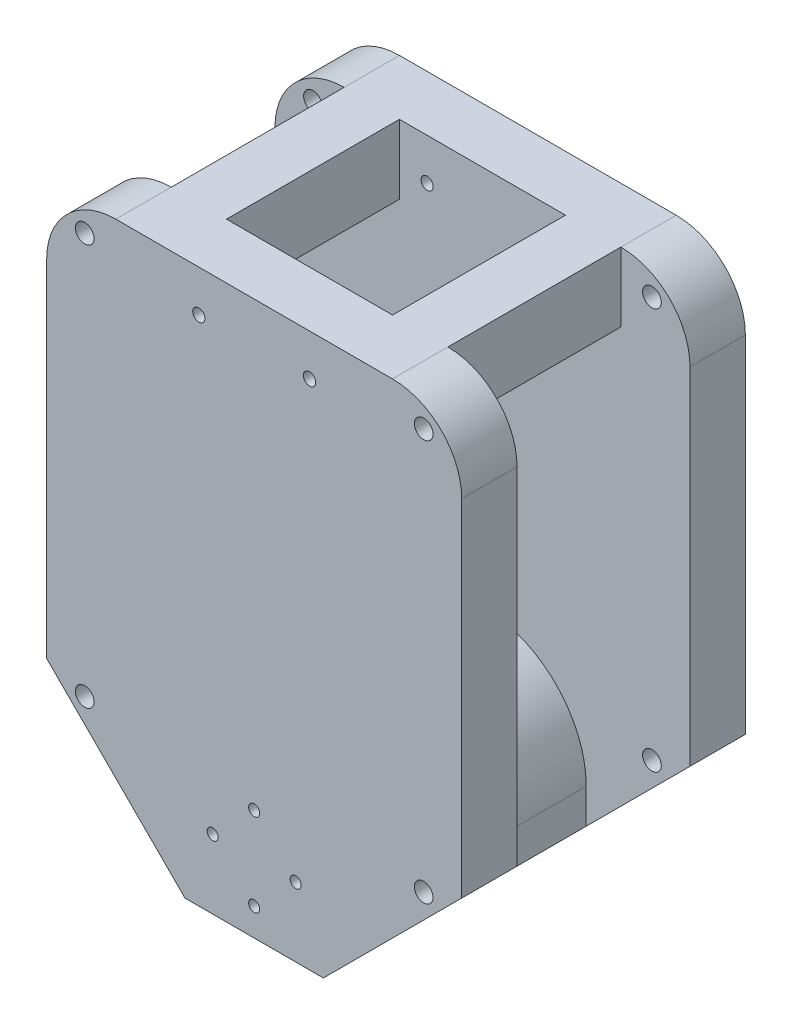
SolidWorks part; units mm, degrees
ref_plane "Front Plane" through (0, 0, 0) normal (0, 0, 1) x (1, 0, 0)
ref_plane "Top Plane" through (0, 0, 0) normal (0, 1, 0) x (1, 0, 0)
ref_plane "Right Plane" through (0, 0, 0) normal (1, 0, 0) x (0, 0, -1)
sketch "Sketch1" plane through (0, 0, 0) normal (0, 0, 1) x (1, 0, 0)
  line L11 (-30, 20.2064) -> (0, 20.2064)
  line L12 (0, 20.2064) -> (30, 20.2064)
  line L13 (30, 20.2064) -> (30, -59.7936)
  line L14 (30, -59.7936) -> (-30, -59.7936)
  line L15 (-30, -59.7936) -> (-30, 20.2064)
  circle A0 centre (-8, 14.2064) radius 0.8836
  circle A1 centre (8, 14.2064) radius 0.8966
  circle A2 centre (0, -49.7936) radius 8 construction
  circle A3 centre (0, -49.7936) radius 6 construction
  circle A4 centre (0, -43.7936) radius 0.8
  circle A5 centre (6, -49.7936) radius 0.8
  circle A6 centre (0, -55.7936) radius 0.8
  circle A7 centre (-6, -49.7936) radius 0.8
  circle A8 centre (-24.5, 16.2064) radius 1.35
  circle A9 centre (24.5, 16.2064) radius 1.35
  circle A10 centre (-24.5, -41.7936) radius 1.35
  circle A11 centre (24.5, -41.7936) radius 1.35
  point P25 (0, -49.7936)
  dimension "D7" = 4
  dimension "D10" = 49
  dimension "D1" = 8
  dimension "D2" = 30
  dimension "D3" = 30
  dimension "D4" = 16
  dimension "D5" = 0
  dimension "D6" = 80
  dimension "D8" = 10
  dimension "D9" = 6
  dimension "D11" = 24.5
  dimension "D12" = 58
  dimension "D13" = 4
extrude "Boss-Extrude1" add sketch "Sketch1" along normal blind 8
sketch "Sketch2" plane through (0, 0, 8) normal (0, 0, 1) x (1, 0, 0)
  line L0 (-12, 20.2064) -> (-12, 10.2064)
  line L1 (30, 20.2064) -> (-30, 20.2064) construction
  line L2 (12, 20.2064) -> (12, 10.2064)
  line L3 (12, 20.2064) -> (20, 20.2064)
  line L4 (20, 20.2064) -> (20, 10.2064)
  line L5 (20, 10.2064) -> (12, 10.2064)
  line L6 (-12, 20.2064) -> (-20, 20.2064)
  line L7 (-20, 20.2064) -> (-20, 10.2064)
  line L8 (-20, 10.2064) -> (-12, 10.2064)
  dimension "D1" = 12
  dimension "D2" = 12
  dimension "D3" = 10
  dimension "D4" = 8
  dimension "D5" = 8
extrude "Boss-Extrude3" add sketch "Sketch2" along normal blind 25
extrude "Boss-Extrude4" add sketch "Sketch1<2>" against normal blind 8 from offset 41
sketch "Sketch1<2>" plane through (0, 0, 0) normal (0, 0, 1) x (1, 0, 0) same geometry as "Sketch1"
sketch "Sketch3" plane through (0, 0, 8) normal (0, 0, 1) x (1, 0, 0)
  line L4 (-30, -59.7936) -> (-10, -59.7936) construction
  line L5 (-6, -49.7936) -> (6, -49.7936) construction
  line L6 (-10, -49.7936) -> (-10, -59.7936)
  line L7 (0, -43.7936) -> (0, -55.7936) construction
  line L8 (10, -49.7936) -> (10, -59.7936)
  line L9 (10, -59.7936) -> (30, -59.7936) construction
  line L10 (-10, -59.7936) -> (10, -59.7936)
  arc A1 (10, -49.7936) -> (-10, -49.7936) centre (0, -49.7936) ccw
extrude "Cut-Extrude1" cut sketch "Sketch3" against normal blind 3
extrude "Cut-Extrude2" cut sketch "Sketch3<2>" along normal blind 3 from surface starting at face at (25.85, -41.7936, 33)
sketch "Sketch3<2>" plane through (0, 0, 8) normal (0, 0, 1) x (1, 0, 0) same geometry as "Sketch3"
sketch "Sketch4" plane through (0, 0, 33) normal (0, 0, -1) x (-1, 0, 0)
  line L0 (-15, -49.7936) -> (-15, -59.7936)
  line L1 (15, -49.7936) -> (15, -59.7936)
  line L2 (-10, -49.7936) -> (-10, -59.7936)
  line L3 (15, -59.7936) -> (30, -59.7936)
  line L4 (-15, -59.7936) -> (-10, -59.7936)
  line L5 (10, -49.7936) -> (10, -59.7936)
  line L6 (-15, -59.7936) -> (-10, -59.7936)
  line L7 (10, -59.7936) -> (15, -59.7936)
  line L8 (15, -59.7936) -> (10, -59.7936)
  line L10 (-15, -59.7936) -> (-10, -59.7936)
  line L11 (10, -59.7936) -> (15, -59.7936)
  line L15 (-30, -59.7936) -> (-10, -59.7936)
  line L16 (-10, -59.7936) -> (-10, -49.7936)
  line L17 (10, -49.7936) -> (10, -59.7936)
  line L18 (10, -59.7936) -> (30, -59.7936)
  line L19 (30, -59.7936) -> (30, 20.2064)
  line L20 (30, 20.2064) -> (20, 20.2064)
  line L21 (20, 20.2064) -> (20, 10.2064)
  line L22 (20, 10.2064) -> (12, 10.2064)
  line L23 (12, 10.2064) -> (12, 20.2064)
  line L24 (12, 20.2064) -> (-12, 20.2064)
  line L25 (-12, 20.2064) -> (-12, 10.2064)
  line L26 (-12, 10.2064) -> (-20, 10.2064)
  line L27 (-20, 10.2064) -> (-20, 20.2064)
  line L28 (-20, 20.2064) -> (-30, 20.2064)
  line L29 (-30, 20.2064) -> (-30, -59.7936)
  line L30 (-30, -59.7936) -> (-15, -59.7936)
  line L34 (30, -59.7936) -> (30, 20.2064)
  line L35 (30, 20.2064) -> (20, 20.2064)
  line L36 (20, 20.2064) -> (20, 10.2064)
  line L37 (20, 10.2064) -> (12, 10.2064)
  line L38 (12, 10.2064) -> (12, 20.2064)
  line L39 (12, 20.2064) -> (-12, 20.2064)
  line L40 (-12, 20.2064) -> (-12, 10.2064)
  line L41 (-12, 10.2064) -> (-20, 10.2064)
  line L42 (-20, 10.2064) -> (-20, 20.2064)
  line L43 (-20, 20.2064) -> (-30, 20.2064)
  line L44 (-30, 20.2064) -> (-30, -59.7936)
  arc A0 (15, -49.7936) -> (-15, -49.7936) centre (0, -49.7936) ccw
  arc A1 (10, -49.7936) -> (-10, -49.7936) centre (0, -49.7936) ccw
  arc A2 (10, -49.7936) -> (-10, -49.7936) centre (0, -49.7936) ccw
  arc A3 (10, -49.7936) -> (-10, -49.7936) centre (0, -49.7936) ccw
  arc A4 (-10, -49.7936) -> (9.3304, -53.3913) centre (0, -49.7936) cw
  dimension "D1" = 0
sketch "Sketch5" plane through (0, 0, 33) normal (0, 0, -1) x (-1, 0, 0)
  line L0 (-15, -49.7936) -> (-15, -59.7936)
  line L1 (-15, -59.7936) -> (-10, -59.7936)
  line L2 (-10, -59.7936) -> (-10, -49.7936)
  line L3 (10, -49.7936) -> (10, -59.7936)
  line L4 (10, -59.7936) -> (15, -59.7936)
  line L5 (15, -59.7936) -> (15, -49.7936)
  arc A0 (10, -49.7936) -> (-10, -49.7936) centre (0, -49.7936) ccw
  arc A1 (15, -49.7936) -> (-15, -49.7936) centre (0, -49.7936) ccw
extrude "Boss-Extrude5" add sketch "Sketch5" along normal blind 25
sketch "Sketch7" plane through (0, 0, 41) normal (0, 0, 1) x (1, 0, 0)
  line L1 (30, 20.2064) -> (30, -59.7936) construction
  line L2 (30, -39.7936) -> (30, -59.7936)
  line L6 (-30, -59.7936) -> (-30, 20.2064) construction
  line L7 (-30, -39.7936) -> (-30, -59.7936)
  line L8 (-30, -39.7936) -> (-10, -59.7936)
  line L9 (10, -59.7936) -> (30, -39.7936)
  line L10 (-30, -59.7936) -> (-10, -59.7936)
  line L11 (10, -59.7936) -> (30, -59.7936)
  dimension "D1" = 20
extrude "Cut-Extrude3" cut sketch "Sketch7" against normal blind 41
fillet "Fillet5" radius 10 4 edges at (-30, 20.2064, 37) (-30, 20.2064, 4) (30, 20.2064, 4) (30, 20.2064, 37)
sketch "Sketch8" plane through (0, 0, 41) normal (0, 0, 1) x (1, 0, 0)
  line L0 (20, 20.2064) -> (-20, 20.2064) construction
  line L1 (-23, 5.2064) -> (23, 5.2064)
  line L2 (-23, 5.2064) -> (-23, -34.7936)
  line L3 (-23, -34.7936) -> (23, -34.7936)
  line L4 (23, 5.2064) -> (23, -34.7936)
  dimension "D1" = 46
  dimension "D2" = 23
  dimension "D3" = 15
  dimension "D4" = 40
